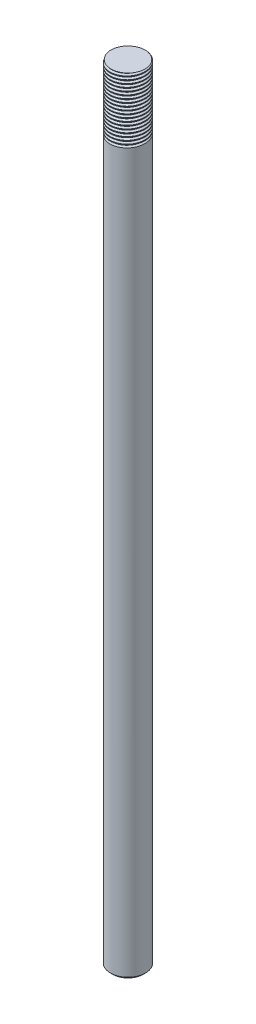
SolidWorks part; units mm, degrees
material "AISI 1020"
ref_plane "Plano superior" through (0, 0, 0) normal (0, 0, 1) x (1, 0, 0)
ref_plane "Plano frontal" through (0, 0, 0) normal (0, 1, 0) x (1, 0, 0)
ref_plane "Plano direito" through (0, 0, 0) normal (1, 0, 0) x (0, 0, -1)
sketch "Esboço1" plane through (0, 0, 0) normal (0, 1, 0) x (1, 0, 0)
  circle A0 centre (0, 0) radius 8
  dimension "D1" = 16
extrude "Ressalto-extrusão1" add sketch "Esboço1" along normal blind 360
thread "Rosca1" pitch 1.5 method cut profile "Perfil da rosca1" start angle 0, offset 0, length 0, pitch 1.5, diameter 16
ref_plane "Plano1" through (-8, 360, 0) normal (0, 0, -1) x (1, 0, 0)
sketch "Perfil da rosca1" plane through (-8, 360, 0) normal (0, 0, -1) x (1, 0, 0)
  line L0 (0, 0) -> (0, 1.5) construction
  line L1 (0, 0) -> (0.8119, 0.4687)
  line L2 (0.8119, 0.4687) -> (0.8119, 0.6562)
  line L3 (0.8119, 0.6562) -> (0, 1.125)
  line L4 (0.8119, 0.5625) -> (0, 0.5625) construction
  line L11 (0, 0) -> (0, 1.125)
  point P2 (0, 0)
  dimension "Pitch" = 1.5
  dimension "Profile_Angle" = 60
  dimension "Profile_Land" = 0.1875
  dimension "Profile_Height" = 0.8119
sketch "Esboço10" plane through (0, 360, 0) normal (0, 1, 0) x (1, 0, 0)
  circle A0 centre (0, 0) radius 8.9812
extrude "Corte-extrusão1" cut sketch "Esboço10" against normal blind 1.5
chamfer "Chanfro1" distance 1 angle 45 1 edges at (0, 0, 8)
